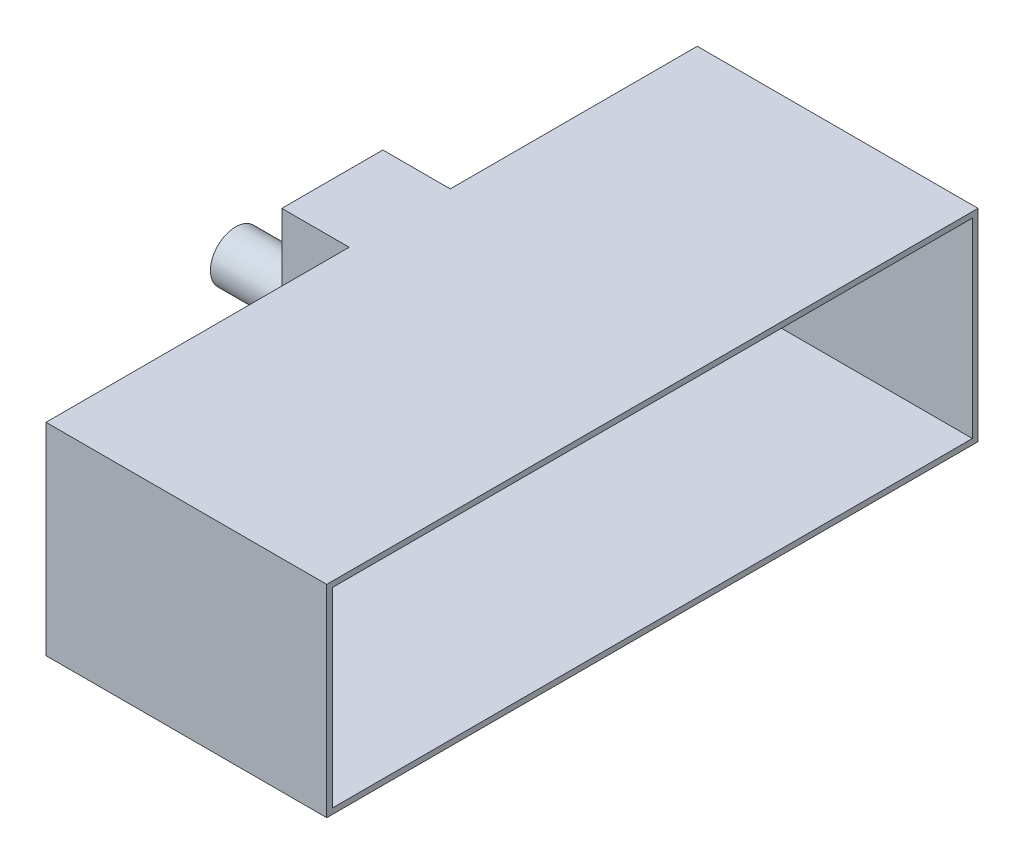
SolidWorks part; units mm, degrees
ref_plane "Front" through (0, 0, 0) normal (0, 0, 1) x (1, 0, 0)
ref_plane "Top" through (0, 0, 0) normal (0, 1, 0) x (1, 0, 0)
ref_plane "Right" through (0, 0, 0) normal (1, 0, 0) x (0, 0, -1)
ref_plane "Plane1" through (82, 0, 0) normal (1, 0, 0) x (0, 0, -1)
sketch "Sketch2" plane through (82, 0, 0) normal (1, 0, 0) x (0, 0, -1)
  circle A0 centre (-66.8797, 39.201) radius 2.25
  arc A1 (-66.8797, 36.951) -> (-66.8797, 41.451) centre (-66.8797, 39.201) ccw construction
  circle A2 centre (-66.8797, 39.201) radius 1.75
  dimension "D1" = 4.5
  dimension "D2" = 3.5
ref_plane "Plane2" through (90.236, 0, 0) normal (1, 0, 0) x (0, 0, -1)
extrude "Boss-Extrude1" add sketch "Sketch2" along normal up to surface (8.236 mm away) up to plane "Plane2"
sketch "Sketch3" plane through (90.236, 0, 0) normal (1, 0, 0) x (0, 0, -1)
  line L0 (-71.5047, 46.8478) -> (-71.5047, 34.0575) construction
  line L1 (-71.0047, 49.0575) -> (-62.0047, 49.0575)
  line L2 (-71.0047, 49.0575) -> (-71.0047, 31.0575)
  line L3 (-71.0047, 31.0575) -> (-62.0047, 31.0575)
  line L4 (-62.0047, 49.0575) -> (-62.0047, 31.0575)
  line L5 (-61.5047, 49.5575) -> (-61.5047, 46.8478) construction
  line L6 (-71.5047, 49.5575) -> (-61.5047, 49.5575) construction
  line L7 (-71.5047, 30.5575) -> (-61.5047, 30.5575) construction
  line L9 (-70.5047, 48.5575) -> (-62.5047, 48.5575)
  line L10 (-70.5047, 48.5575) -> (-70.5047, 31.5575)
  line L11 (-70.5047, 31.5575) -> (-62.5047, 31.5575)
  line L12 (-62.5047, 48.5575) -> (-62.5047, 31.5575)
  circle A0 centre (-66.8797, 39.201) radius 1.75
  circle A1 centre (-66.8797, 39.201) radius 1.75 construction
  dimension "D1" = 0.5
  dimension "D2" = 0.5
  dimension "D3" = 0.5
  dimension "D4" = 0.5
  dimension "D5" = 0.5
  dimension "D6" = 0.5
  dimension "D7" = 0.5
  dimension "D8" = 0.5
extrude "Boss-Extrude2" add sketch "Sketch3" along normal blind 6 separate body contours L4 L1 L2 L3 L9 L12 L11 L10 region at (90.236, 48.8563, 66.5047)
sketch "Sketch4" plane through (96.236, 0, 0) normal (1, 0, 0) x (0, 0, -1)
  line L0 (-71.0047, 49.0575) -> (-62.0047, 49.0575) construction
  line L1 (-98.0047, 49.0575) -> (-40.0047, 49.0575)
  line L2 (-98.0047, 49.0575) -> (-98.0047, 31.0575)
  line L3 (-98.0047, 31.0575) -> (-40.0047, 31.0575)
  line L4 (-40.0047, 49.0575) -> (-40.0047, 31.0575)
  line L5 (-71.0047, 31.0575) -> (-62.0047, 31.0575) construction
  line L7 (-71.0047, 49.0575) -> (-71.0047, 31.0575) construction
  line L8 (-62.0047, 49.0575) -> (-62.0047, 31.0575) construction
  line L10 (-97.5047, 48.5575) -> (-40.5047, 48.5575)
  line L11 (-97.5047, 48.5575) -> (-97.5047, 31.5575)
  line L12 (-97.5047, 31.5575) -> (-40.5047, 31.5575)
  line L13 (-40.5047, 48.5575) -> (-40.5047, 31.5575)
  line L18 (-70.5047, 48.5575) -> (-62.5047, 48.5575)
  line L19 (-70.5047, 48.5575) -> (-70.5047, 31.5575)
  line L20 (-70.5047, 31.5575) -> (-62.5047, 31.5575)
  line L21 (-62.5047, 48.5575) -> (-62.5047, 31.5575)
  line M5 (-62.0047, 31.0575) -> (-62.0047, 49.0575)
  line M6 (-62.0047, 49.0575) -> (-71.0047, 49.0575)
  line M7 (-71.0047, 49.0575) -> (-71.0047, 31.0575)
  line M8 (-71.0047, 31.0575) -> (-62.0047, 31.0575)
  line M9 (-70.5047, 48.5575) -> (-62.5047, 48.5575)
  line M10 (-62.5047, 48.5575) -> (-62.5047, 31.5575)
  line M11 (-62.5047, 31.5575) -> (-70.5047, 31.5575)
  line M12 (-70.5047, 31.5575) -> (-70.5047, 48.5575)
  dimension "D1" = 27
  dimension "D2" = 22
  dimension "D3" = 0.5
  dimension "D4" = 0.5
  dimension "D5" = 0.5
  dimension "D6" = 0.5
extrude "Boss-Extrude4" add sketch "Sketch3<3>" along normal blind 0.5 contours L12 L9 L10 L11 A0 region at (90.236, 48.3696, 66.5047)
sketch "Sketch3<3>" plane through (90.236, 0, 0) normal (1, 0, 0) x (0, 0, -1) same geometry as "Sketch3"
extrude "Boss-Extrude5" add sketch "Sketch4" along normal blind 0.5 contours L12 L11 L10 L1 L2 L3 M7 | L11 L12 L10 M7 | L10 M7 M9 M5 M6 | L12 L10 M7 M12 | L12 M7 M8 M5 M11 | L12 L10 M10 M5 | L13 L10 L12 M5 | L10 L13 L12 L3 L4 L1 M5 region at (96.236, 48.733, 84.5047) region at (96.236, 48.8075, 66.5047) region at (96.236, 48.7733, 51.0047) region at (96.236, 40.0575, 84.2547) region at (96.236, 40.0575, 70.7547) region at (96.236, 31.3075, 66.5047) region at (96.236, 40.0575, 62.2547) region at (96.236, 40.0575, 51.2547)
extrude "Boss-Extrude6" add sketch "Sketch4<4>" along normal blind 25 contours L10 M7 M9 M5 M6 | L12 L11 L10 L1 L2 L3 M7 | L10 L13 L12 L3 L4 L1 M5 | L12 M7 M8 M5 M11 region at (96.236, 48.733, 84.5047) region at (96.236, 48.8075, 66.5047) region at (96.236, 48.7733, 51.0047) region at (96.236, 31.3075, 66.5047)
sketch "Sketch4<4>" plane through (96.236, 0, 0) normal (1, 0, 0) x (0, 0, -1) same geometry as "Sketch4"
